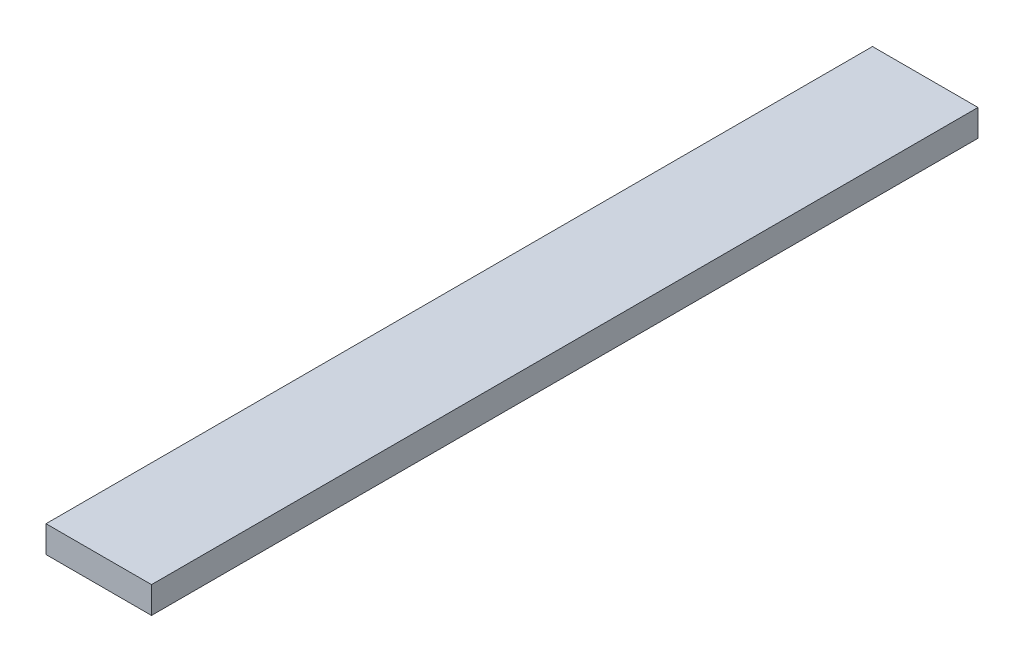
SolidWorks part; units mm, degrees
ref_plane "Front Plane" through (0, 0, 0) normal (0, 0, 1) x (1, 0, 0)
ref_plane "Top Plane" through (0, 0, 0) normal (0, 1, 0) x (1, 0, 0)
ref_plane "Right Plane" through (0, 0, 0) normal (1, 0, 0) x (0, 0, -1)
sketch "Motor Asm - Side Profile" plane through (0, 0, 0) normal (0, 0, 1) x (1, 0, 0)
  line L1 (17.5, 20.95) -> (54.5, 20.95)
  line L3 (54.5, 20.95) -> (54.5, 21)
  line L5 (54.5, 21) -> (57.0147, 21)
  line L7 (57.0147, 21) -> (57.0147, 23)
  line L9 (57.0147, 23) -> (63.0455, 23)
  line L11 (63.0455, 23) -> (63.0455, 21)
  line L13 (63.0455, 21) -> (65.2, 21)
  line L15 (65.5, 20.7) -> (65.5, 15.8757)
  line L17 (65.5, 15.8757) -> (65.5, -15.8757)
  line L19 (65.5, -15.8757) -> (65.5, -20.7)
  line L21 (65.2, -21) -> (54.5, -21)
  line L23 (54.5, -21) -> (54.5, -20.95)
  line L25 (54.5, -20.95) -> (44.0354, -20.95)
  line L27 (44.0354, -20.95) -> (46, -23.45)
  line L29 (46, -23.45) -> (46, -27.45)
  line L31 (46, -27.45) -> (-21, -27.45)
  line L33 (-21, -27.45) -> (-21, -23.45)
  line L35 (-21, -23.45) -> (-21, -11.52)
  line L37 (-21, -11.52) -> (-21, -5.17)
  line L39 (-21, -5.17) -> (-18, -5.17)
  line L41 (-18, -5.17) -> (-18, 7.5)
  line L43 (-18, 7.5) -> (-17.2933, 7.5)
  line L45 (-17.2933, 7.5) -> (-17, 6.4494)
  line L47 (-17, 6.4494) -> (-17, 6.026)
  line L49 (-17, 6.026) -> (-10, 6.026)
  line L51 (-10, 6.026) -> (-10, 6.4494)
  line L53 (-10, 6.4494) -> (-9.7067, 7.5)
  line L55 (-9.7067, 7.5) -> (-4.2067, 7.5)
  line L57 (-4.2067, 7.5) -> (-4, 7.2956)
  line L59 (-4, 7.2956) -> (-4, 1.75)
  line L61 (-4, 1.75) -> (-3, 1.75)
  line L63 (-3, 1.75) -> (-3, 2.5)
  line L65 (-3, 2.5) -> (0, 2.5)
  line L67 (0, 2.5) -> (0, 27.45)
  line L69 (0, 27.45) -> (6, 27.45)
  line L71 (6, 27.45) -> (11.0688, 21)
  line L73 (11.0688, 21) -> (17.5, 21)
  line L75 (17.5, 21) -> (17.5, 20.95)
  line L77 (-17, -6.026) -> (-17, -6.4494)
  line L79 (-17, -6.4494) -> (-17.2933, -7.5)
  line L81 (-17.2933, -7.5) -> (-18, -7.5)
  line L83 (-18, -7.5) -> (-18, 7.5)
  line L85 (-18, 7.5) -> (-17.2933, 7.5)
  line L87 (-17.2933, 7.5) -> (-17, 6.4494)
  line L89 (-17, 6.4494) -> (-17, 6.026)
  line L91 (-17, 6.026) -> (-10, 6.026)
  line L93 (-10, 6.026) -> (-10, 6.4494)
  line L95 (-10, 6.4494) -> (-9.7067, 7.5)
  line L97 (-9.7067, 7.5) -> (-4.2067, 7.5)
  line L99 (-4.2067, 7.5) -> (-4, 7.2956)
  line L101 (-4, 7.2956) -> (-4, -7.2956)
  line L103 (-4, -7.2956) -> (-4.2067, -7.5)
  line L105 (-4.2067, -7.5) -> (-9.7067, -7.5)
  line L107 (-9.7067, -7.5) -> (-10, -6.4494)
  line L109 (-10, -6.4494) -> (-10, -6.026)
  line L111 (-10, -6.026) -> (-17, -6.026)
  line L113 (-10.5, -5.8538) -> (-10.5, -5.9412)
  line L115 (-10.5, -5.9412) -> (-10.5, -6.0911)
  line L117 (-10.5, -6.0911) -> (-10.5, -6.85)
  line L119 (-10.5, -6.85) -> (-16.5, -6.85)
  line L121 (-16.5, -6.85) -> (-16.5, -6.09)
  line L123 (-16.5, -6.09) -> (-16.5, -5.9412)
  line L125 (-16.5, -5.9412) -> (-16.5, -5.8526)
  line L127 (-16.5, -5.8526) -> (-16.5, -5.33)
  line L129 (-16.5, -5.33) -> (-10.5, -5.33)
  line L131 (-10.5, -5.33) -> (-10.5, -5.8538)
  line L133 (-6, -5.17) -> (-6, -23.45)
  line L137 (-21, -11.52) -> (-21, -5.17)
  line L139 (-21, -5.17) -> (-16.6, -5.17)
  line L141 (-16.6, -5.17) -> (-16.6, -6.85)
  line L143 (-16.6, -6.85) -> (-10.4, -6.85)
  line L145 (-10.4, -6.85) -> (-10.4, -5.17)
  line L147 (-10.4, -5.17) -> (-6, -5.17)
  line L148 (-6, -23.45) -> (46, -23.45)
  line L150 (0, -23.45) -> (0, -2.5)
  line L153 (0, -2.5) -> (-4, -2.5)
  line L155 (11.0688, 21) -> (44.0354, -20.95)
  arc A1 (65.5, 20.7) -> (65.2, 21) centre (65.2, 20.7) ccw
  arc A3 (65.2, -21) -> (65.5, -20.7) centre (65.2, -20.7) ccw
sketch "Sketch2" plane through (0, 0, 0) normal (0, 0, 1) x (1, 0, 0)
  line L0 (-10.5, -6.0911) -> (-10.5, -6.85) construction
  line L4 (-16.5, -5.33) -> (-10.5, -5.33) construction
  line L8 (-16.5, -6.85) -> (-16.5, -6.09) construction
  line L9 (-10.5, -6.85) -> (-16.5, -6.85) construction
  line L10 (-10.5, -5.33) -> (-10.5, -6.85)
  line L14 (-16.5, -5.33) -> (-10.5, -5.33)
  line L18 (-16.5, -6.85) -> (-16.5, -5.33)
  line L19 (-10.5, -6.85) -> (-16.5, -6.85)
  point P2 (-10.5, -5.8206)
  point P3 (-16.5, -5.3503)
  point P9 (-10.5, -5.3872)
extrude "Boss-Extrude1" add sketch "Sketch2" along normal blind 37 and the other way blind 10
